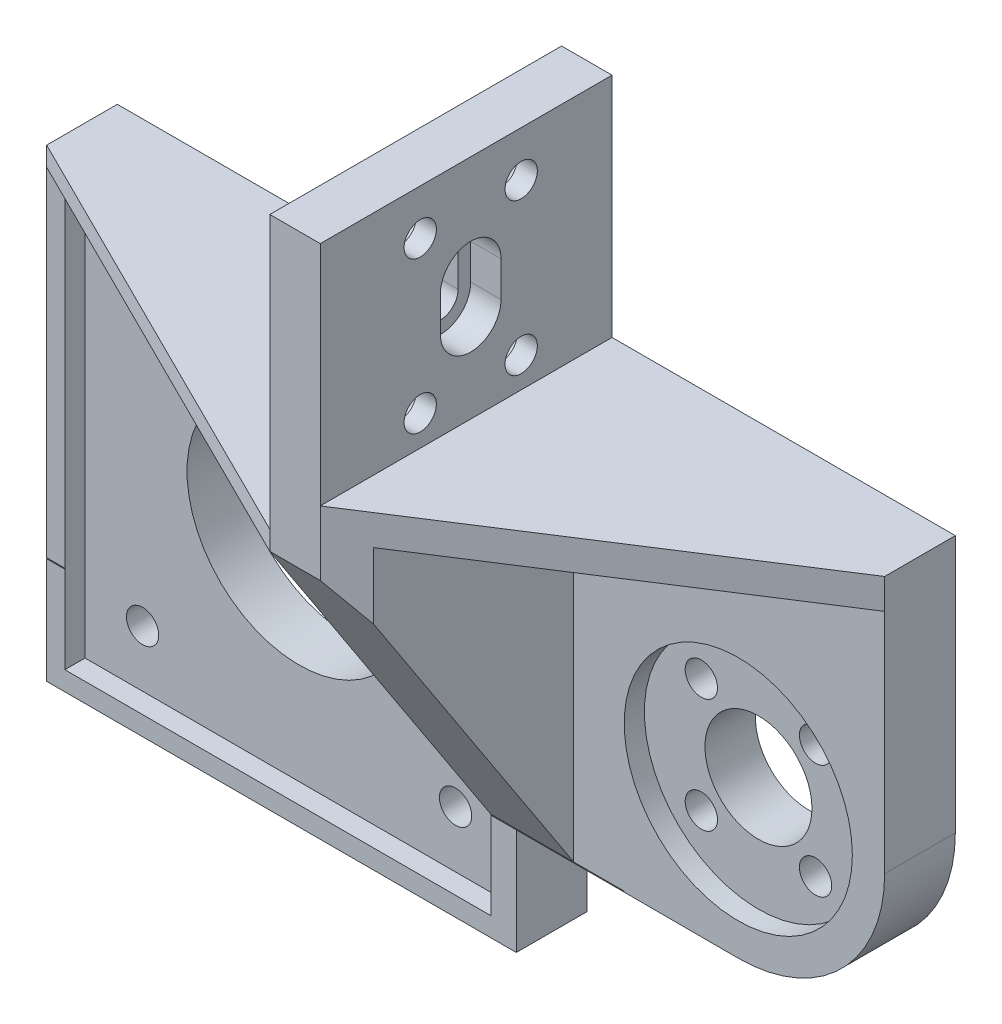
SolidWorks part; units mm, degrees
ref_plane "前视基准面" through (0, 0, 0) normal (0, 0, 1) x (1, 0, 0)
ref_plane "上视基准面" through (0, 0, 0) normal (0, 1, 0) x (1, 0, 0)
ref_plane "右视基准面" through (0, 0, 0) normal (1, 0, 0) x (0, 0, -1)
sketch "草图1" plane through (0, 0, 0) normal (0, 0, 1) x (1, 0, 0)
  line L1 (-68.5, 26) -> (-24.5, 26)
  line L2 (-68.5, 26) -> (-68.5, -25)
  line L3 (-68.5, -25) -> (14.5, -25)
  line L4 (14.5, 25.5) -> (14.5, -25)
  line L5 (-24.5, 71) -> (-19.5, 71)
  line L6 (-24.5, 71) -> (-24.5, 26)
  line L7 (14.5, 25.5) -> (-19.5, 25.5)
  line L8 (-19.5, 71) -> (-19.5, 26)
  line L9 (-19.5, 25.5) -> (-19.5, 26)
  circle A0 centre (0, 0) radius 5.3
  circle A1 centre (-45.5, -2) radius 11.1
  dimension "D1" = 10.6
  dimension "D7" = 22.2
  dimension "D2" = 26
  dimension "D3" = 19.5
  dimension "D4" = 45
  dimension "D5" = 5
  dimension "D6" = 21
  dimension "D8" = 28
  dimension "D9" = 51
  dimension "D10" = 23
  dimension "D11" = 34
extrude "凸台-拉伸1" add sketch "草图1" along normal blind 7
sketch "草图2" plane through (0, 0, 7) normal (0, 0, 1) x (1, 0, 0)
  line L0 (-24.5, 71) -> (-24.5, 26) construction
  line L1 (-66.7, 19.1) -> (-24.5, 19.1)
  line L2 (-66.7, 19.1) -> (-66.7, -23.1)
  line L3 (-66.7, -23.1) -> (-24.5, -23.1)
  line L4 (-24.5, 19.1) -> (-24.5, -23.1)
  line L5 (-45.5, -2) -> (-22.3009, -2) construction
  line L6 (-45.5, -2) -> (-45.5, 9.1) construction
  circle A0 centre (0, 0) radius 11.3
  circle A1 centre (-45.5, -2) radius 11.1 construction
  dimension "D1" = 22.6
  dimension "D2" = 42.2
  dimension "D3" = 42.2
extrude "切除-拉伸1" cut sketch "草图2" against normal blind 2
sketch "草图3" plane through (0, 0, 5) normal (0, 0, 1) x (1, 0, 0)
  line L0 (-45.5, -2) -> (-45.5, 9.1) construction
  line L1 (-45.5, -2) -> (-56.6, -2) construction
  line L2 (0, 0) -> (0, 5.3) construction
  circle A0 centre (-61, 13.5) radius 1.6
  circle A1 centre (-45.5, -2) radius 11.1 construction
  circle A2 centre (-30, 13.5) radius 1.6
  circle A3 centre (-30, -17.5) radius 1.6
  circle A4 centre (-61, -17.5) radius 1.6
  circle A5 centre (5.6569, 5.6569) radius 1.6
  circle A6 centre (-5.6569, 5.6569) radius 1.6
  circle A7 centre (5.6569, -5.6569) radius 1.6
  circle A8 centre (-5.6569, -5.6569) radius 1.6
  circle A9 centre (0, 0) radius 5.3 construction
  point P26 (0, 0)
  dimension "D1" = 3.2
  dimension "D4" = 3.2
  dimension "D2" = 31
  dimension "D3" = 31
  dimension "D5" = 8
  dimension "D6" = 4
extrude "切除-拉伸2" cut sketch "草图3" against normal through all
sketch "草图4" plane through (0, 0, 7) normal (0, 0, 1) x (1, 0, 0)
  line L0 (-24.5, 71) -> (-24.5, 26)
  line L1 (-24.5, 26) -> (-68.5, 26)
  line L2 (-68.5, 26) -> (-68.5, 19.1)
  line L3 (-68.5, 26) -> (-68.5, -25) construction
  line L4 (-68.5, 19.1) -> (-24.5, 19.1)
  line L5 (-24.5, 19.1) -> (-24.5, -14.4796)
  line L6 (-24.5, -23.1) -> (-24.5, 19.1) construction
  line L7 (-24.5, -14.4796) -> (-11.3, -14.4796)
  line L8 (14.5, 25.5) -> (14.5, 22.5)
  line L9 (-19.5, 71) -> (-24.5, 71)
  line L10 (-24.5, 71) -> (-14.8569, 66.0268)
  line L11 (-19.5, 25.5) -> (14.5, 25.5)
  line L12 (14.5, -25) -> (14.5, 25.5) construction
  line L14 (14.5, 22.5) -> (-11.3, 22.5)
  line L15 (-19.5, 25.5) -> (-19.5, 71)
  line L16 (-11.3, 22.5) -> (-11.3, -14.8517)
  circle A0 centre (0, 0) radius 11.3 construction
  line M2 (-66.7, 19.1) -> (-24.5, 19.1)
  line M3 (-24.5, 19.1) -> (-24.5, -23.1)
  line M6 (-68.5, 26) -> (-68.5, -25)
  line M8 (14.5, -25) -> (14.5, 25.5)
  line M9 (14.5, 25.5) -> (-19.5, 25.5)
  line M10 (-19.5, 25.5) -> (-19.5, 71)
  line M11 (-19.5, 71) -> (-24.5, 71)
  line M12 (-24.5, 71) -> (-24.5, 26)
  line M13 (-24.5, 26) -> (-68.5, 26)
  dimension "D1" = 3
extrude "凸台-拉伸2" add sketch "草图4" along normal blind 21.9 contours L16 L14 L4 L7 M8 M9 M10 M11 M12 M13 M6 M2 M3 region at (-25.0565, 19.5935, 7)
sketch "草图5" plane through (-11.3, 0, 0) normal (1, 0, 0) x (0, 0, -1)
  line L0 (-28.9, 19.1) -> (-28.9, -14.4796)
  line L1 (-28.9, -14.4796) -> (-7, -14.4796)
  line L2 (-28.9, 19.1) -> (-6.9823, -14.4208)
  line L3 (-7, -14.4796) -> (-6.9823, -14.4208)
extrude "切除-拉伸3" cut sketch "草图5" against normal through all
sketch "草图6" plane through (0, 22.5, 0) normal (0, -1, 0) x (1, 0, 0)
  line L0 (-68.5, 7) -> (-24.5, 28.9)
  line L1 (-24.5, 6.9823) -> (-24.5, 28.9) construction
  line L2 (-68.5, 28.9) -> (-24.5, 28.9) construction
  line L3 (-24.5, 28.9) -> (-68.5, 28.9)
  line L4 (-68.5, 28.9) -> (-68.5, 7)
  line L5 (-19.5, 28.9) -> (14.5, 7)
  line L6 (14.5, 7) -> (14.5, 28.9)
  line L7 (14.5, 28.9) -> (-19.5, 28.9)
  line M2 (14.5, 7) -> (14.5, 28.9)
  line M3 (14.5, 28.9) -> (-11.3, 28.9)
  line M4 (-11.3, 28.9) -> (-11.3, 7)
  dimension "D1" = 32.786
extrude "切除-拉伸4" cut sketch "草图6" against normal blind 10 and the other way through all contours M3 M2 | L3 L4 L0 | L7 L5 M4 region at (-53.8333, 22.5, 21.6) region at (-14.0333, 22.5, 27.1394) region at (4.2289, 22.5, 21.2579)
sketch "草图7" plane through (0, 0, 7) normal (0, 0, 1) x (1, 0, 0)
  line L0 (-13.15, -14.4796) -> (-11.3, -14.4796)
  line L1 (21.147, 0) -> (14.5, 0)
  line L2 (-13.15, -14.4796) -> (-13.15, -44.4594)
  line L3 (-13.15, -44.4594) -> (22.7686, -44.4594)
  line L4 (22.7686, -44.4594) -> (21.147, 0)
  line L5 (-11.3, -14.4796) -> (-0.0262, -14.5)
  line L6 (14.5, -25) -> (14.5, 25.5) construction
  arc A0 (-0.0262, -14.5) -> (14.5, 0) centre (0, 0) ccw
extrude "切除-拉伸5" cut sketch "草图7" against normal through all
sketch "草图8" plane through (-24.5, 0, 0) normal (-1, 0, 0) x (0, 0, 1)
  line L0 (0, 36) -> (28.9, 36) construction
  line L1 (0, 71) -> (0, 26) construction
  line L2 (28.9, 71) -> (28.9, 26) construction
  line L3 (28.9, 26) -> (0, 26) construction
  line L5 (14, 63.1654) -> (14, 16) construction
  line L6 (7, 26) -> (0, 26) construction
  line L7 (-5.9715, 74.3768) -> (35.7081, 74.3768)
  line L8 (-5.9715, 74.3768) -> (-5.9715, 48)
  line L9 (-5.9715, 48) -> (35.7081, 48)
  line L10 (35.7081, 74.3768) -> (35.7081, 48)
  line L11 (15.75, 37.75) -> (15.75, 34.25)
  line L13 (12.25, 34.25) -> (12.25, 37.75)
  circle A0 centre (19, 28.5) radius 1.6
  circle A1 centre (19, 43.5) radius 1.6
  circle A2 centre (9, 28.5) radius 1.6
  circle A3 centre (9, 43.5) radius 1.6
  arc A4 (15.75, 37.75) -> (12.25, 37.75) centre (14, 37.75) ccw
  arc A7 (15.75, 34.25) -> (12.25, 34.25) centre (14, 34.25) cw
  dimension "D2" = 3.2
  dimension "D6" = 3.5
  dimension "D1" = 10
  dimension "D3" = 10
  dimension "D4" = 15
  dimension "D5" = 22
  dimension "D7" = 3.5
  dimension "D8" = 14
extrude "切除-拉伸6" cut sketch "草图8" against normal through all
sketch "草图9" plane through (-24.5, 0, 0) normal (-1, 0, 0) x (0, 0, 1)
  circle A0 centre (9, 43.5) radius 3
  circle A1 centre (19, 43.5) radius 3
  circle A2 centre (9, 28.5) radius 3
  circle A3 centre (19, 28.5) radius 3
  dimension "D1" = 6
  dimension "D2" = 6
  dimension "D3" = 6
  dimension "D4" = 6
extrude "切除-拉伸7" cut sketch "草图9" against normal blind 3
sketch "草图10" plane through (-19.5, 0, 0) normal (1, 0, 0) x (0, 0, -1)
  line L0 (-11, 37.75) -> (-11, 34.25)
  line L1 (-17, 37.75) -> (-17, 34.25)
  arc A0 (-11, 37.75) -> (-17, 37.75) centre (-14, 37.75) ccw
  arc A1 (-17, 34.25) -> (-11, 34.25) centre (-14, 34.25) ccw
  dimension "D1" = 6
  dimension "D2" = 6
extrude "切除-拉伸8" cut sketch "草图10" against normal blind 3
sketch "草图11" plane through (0, 0, 0) normal (0, 0, -1) x (-1, 0, 0)
  line L0 (68.5, 26) -> (68.5, -25) construction
  line L1 (24.5, 26) -> (68.5, 26)
  line L2 (24.5, 26) -> (24.5, 21)
  line L3 (24.5, 21) -> (68.5, 21)
  line L4 (68.5, 26) -> (68.5, 21)
  dimension "D1" = 5
extrude "切除-拉伸9" cut sketch "草图11" against normal through all
sketch "草图12" plane through (-11.3, 0, 0) normal (1, 0, 0) x (0, 0, -1)
  line L1 (-7, 22.5) -> (-44.7136, 22.5)
  line L2 (-7, 22.5) -> (-7, -17.5605)
  line L3 (-7, -17.5605) -> (-44.7136, -17.5605)
  line L4 (-44.7136, 22.5) -> (-44.7136, -17.5605)
extrude "切除-拉伸11" cut sketch "草图12" against normal blind 5
sketch "草图13" plane through (0, 0, 7) normal (0, 0, 1) x (1, 0, 0)
  line L0 (-24.5, -14.4796) -> (-13.15, -14.4796) construction
  line L1 (-13.15, -25) -> (-21.9852, -25)
  line L2 (-13.15, -25) -> (-13.15, -14.4796)
  line L3 (-13.15, -14.4796) -> (-21.9852, -14.4796)
  line L4 (-21.9852, -25) -> (-21.9852, -14.4796)
extrude "切除-拉伸12" cut sketch "草图13" against normal through all
